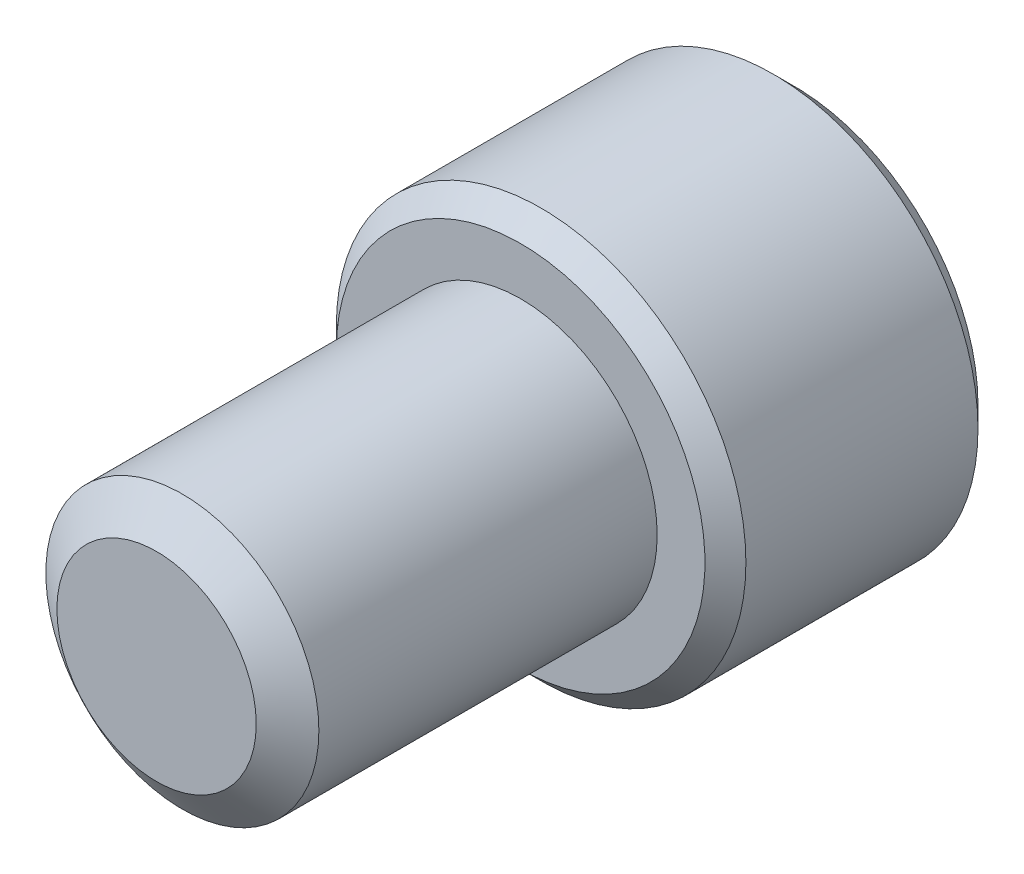
SolidWorks part; units mm, degrees
ref_plane "Front Plane" through (0, 0, 0) normal (0, 0, 1) x (1, 0, 0)
ref_plane "Top Plane" through (0, 0, 0) normal (0, 1, 0) x (1, 0, 0)
ref_plane "Right Plane" through (0, 0, 0) normal (1, 0, 0) x (0, 0, -1)
sketch "Sketch1" plane through (0, 0, 0) normal (0, 0, 1) x (1, 0, 0)
  circle A0 centre (0, 0) radius 4.7625
  dimension "OD" = 9.525
extrude "Extrude1" add sketch "Sketch1" against normal blind 12.7
sketch "Sketch2" plane through (0, 0, 0) normal (0, 0, 1) x (1, 0, 0)
  circle A0 centre (0, 0) radius 4.7625 construction
  circle A1 centre (0, 0) radius 4.7625
curve "Helix/Spiral1" [suppressed] pitch 1.5875 height 14.2875 turns 9 parameters "pitch"=1.5875
sketch "Sketch3" plane through (0, 0, 0) normal (1, 0, 0) x (0, 0, -1)
  line L0 (-1.3891, 4.7625) -> (-0.7937, 3.7314)
  line L1 (-0.7937, 3.7314) -> (-0.5953, 3.7314)
  line L2 (-0.5953, 3.7314) -> (0, 4.7625)
  line L3 (-1.3891, 4.7625) -> (0, 4.7625)
  line L4 (-0.6945, 4.7625) -> (-0.6945, 3.7314) construction
  line L5 (-1.0914, 4.2469) -> (-0.2977, 4.2469) construction
  line L6 (0, 4.7625) -> (0, -4.7625) construction
  dimension "D1" = 0.1984
  dimension "D2" = 0.7937
  dimension "D3" = 60
sweep "Cut-Sweep1" [suppressed] cut profiles "Sketch3" path "Helix/Spiral1"
sketch "Sketch4" plane through (0, 0, 0) normal (1, 0, 0) x (0, 0, -1)
  line L0 (0.8998, 4.7625) -> (0, 3.4774)
  line L1 (0, 3.4774) -> (0, 4.7625)
  line L2 (0.8998, 4.7625) -> (0, 4.7625)
  line L3 (-1.3891, 4.7625) -> (0, 4.7625) construction
  line L4 (0, 0) -> (7.0209, 0) construction
  dimension "D1" = 55
  dimension "D2" = 0.254
revolve "Cut-Revolve1" cut sketch "Sketch4" angle 360 about L4
sketch "Sketch5" [suppressed] plane through (0, 0, 0) normal (1, 0, 0) x (0, 0, -1)
  line L0 (12.7, -3.7535) -> (12.7, 3.3982) construction
  line L1 (12.7, 4.8895) -> (25.5202, 4.8895)
  line L2 (12.7, 4.8895) -> (12.7, 0)
  line L3 (12.7, 0) -> (25.4, 0)
  line L4 (25.4, 4.5593) -> (25.4, 0)
  line L5 (25.5202, 4.8895) -> (25.4, 4.5593)
  line L6 (0, 0) -> (9.9695, 0) construction
  point P3 (25.4, 4.8895)
  point P10 (25.4, 4.8895)
  dimension "D1" = 0.3302
  dimension "Thread min" = 25.4
  dimension "D2" = 0.127
  dimension "D3" = 20
revolve "partially thread" [suppressed] add sketch "Sketch5" angle 360 about L6
sketch "Sketch6" plane through (0, 0, -12.7) normal (0, 0, -1) x (-1, 0, 0)
  circle A0 centre (0, 0) radius 7.1438
  dimension "head dia" = 14.2875
extrude "Extrude2" add sketch "Sketch6" along normal blind 9.525
sketch "Sketch7" plane through (0, 0, -22.225) normal (0, 0, -1) x (-1, 0, 0)
  line L1 (0, 4.5827) -> (-3.9688, 2.2914)
  line L2 (-3.9688, 2.2914) -> (-3.9688, -2.2914)
  line L3 (-3.9688, -2.2914) -> (0, -4.5827)
  line L4 (0, -4.5827) -> (3.9688, -2.2914)
  line L5 (3.9688, -2.2914) -> (3.9688, 2.2914)
  line L6 (3.9688, 2.2914) -> (0, 4.5827)
  circle A0 centre (0, 0) radius 3.9688 construction
  dimension "hex dia" = 7.9375
extrude "Cut-Extrude1" cut sketch "Sketch7" against normal blind 5.9531
sketch "Sketch8" plane through (0, 0, -22.225) normal (0, 0, -1) x (-1, 0, 0)
  circle A0 centre (0, 0) radius 4.5827
extrude "Cut-Extrude2" cut sketch "Sketch8" against normal through all draft 45
chamfer "Chamfer1" distance 0.7144 angle 45 2 edges at (-7.1438, 0, -22.225) (-7.1438, 0, -12.7)
sketch "Sketch9" plane through (0, 0, 0) normal (1, 0, 0) x (0, 0, -1)
  line L0 (0, 4.7625) -> (0, -4.7625) construction
  line L1 (8.7313, 4.7625) -> (8.7313, -4.7625) construction
  dimension "D1" = 8.7312
equation "\"D3@Helix/Spiral1\" = \"screw length@Extrude1\"+\"pitch@Helix/Spiral1\""
equation "\"D1@Sketch3\" = \"pitch@Helix/Spiral1\"*.125"
equation "\"D2@Sketch3\" = \"pitch@Helix/Spiral1\"*.5"
equation "\"D1@Cut-Extrude1\" = \"hex dia@Sketch7\"*.75"
equation "\"D1@Chamfer1\" = \"head dia@Sketch6\"*.05"
equation "\"D1@Sketch9\" = \"pitch@Helix/Spiral1\"*5.5"
